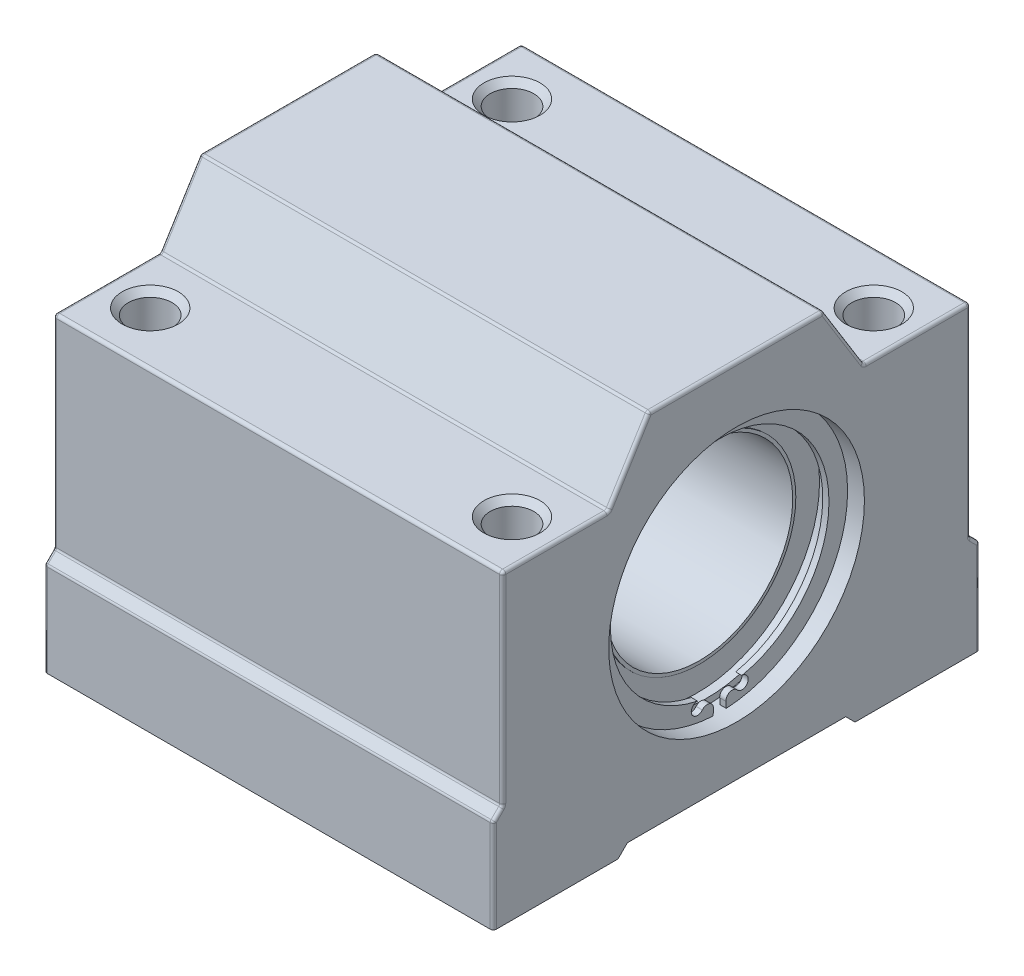
SolidWorks part; units mm, degrees
ref_plane "Front Plane" through (0, 0, 0) normal (0, 0, 1) x (1, 0, 0)
ref_plane "Top Plane" through (0, 0, 0) normal (0, 1, 0) x (1, 0, 0)
ref_plane "Right Plane" through (0, 0, 0) normal (1, 0, 0) x (0, 0, -1)
sketch "Sketch1" plane through (0, 0, 0) normal (1, 0, 0) x (0, 0, -1)
  line L1 (-19, -30) -> (-17.5, -28.5)
  line L2 (-17.5, -28.5) -> (17.5, -28.5)
  line L3 (17.5, -28.5) -> (19, -30)
  line L4 (19, -30) -> (39, -30)
  line L6 (39, -15) -> (37.5, -13.5)
  line L8 (37.5, 19) -> (20.5, 19)
  line L9 (20.5, 19) -> (14, 29.5)
  line L10 (14, 29.5) -> (-14, 29.5)
  line L11 (-14, 29.5) -> (-20.5, 19)
  line L12 (-20.5, 19) -> (-37.5, 19)
  line L15 (-39, -15) -> (-39, -30)
  line L16 (0, -28.5) -> (0, 29.5) construction
  line L17 (-16.278, 0) -> (14.0247, 0) construction
  line L18 (-39, -30) -> (-19, -30)
  line L19 (39, -15) -> (39, -30)
  line L20 (-37.5, -13.5) -> (-37.5, 19)
  line L21 (37.5, -13.5) -> (37.5, 19)
  line L22 (-29, 19) -> (-29, -30) construction
  line L23 (-29, -30) -> (29, 19) construction
  line L24 (29, 19) -> (29, -30) construction
  line L25 (-39, -15) -> (-37.5, -13.5)
  line L26 (-20.5, 0) -> (20.5, 0) construction
  circle A0 centre (0, 0) radius 20.5
  circle A1 centre (0, 0) radius 19.5
  circle A2 centre (0, 0) radius 15
  point P18 (0, 29.5)
  point P23 (0, 0)
  dimension "D12" = 30
  dimension "D1" = 78
  dimension "D2" = 49
  dimension "D3" = 30
  dimension "D5" = 59.5
  dimension "D6" = 58
  dimension "D4" = 15
  dimension "D7" = 1.5
  dimension "D8" = 28
  dimension "D9" = 1.5
  dimension "D10" = 20
  dimension "D11" = 1
extrude "Boss-Extrude1" add sketch "Sketch1" along normal blind 72 contours L25 L15 L18 L1 L2 L3 L4 L19 L6 L21 L8 L9 L10 L11 L12 L20 A0 region at (0, -29.019, 29)
extrude "Extrude-Thin1" add sketch "Sketch1<4>" along normal blind 65.5 from offset 0.5 separate body thin contours A2 thin type one direction wall 0.5
sketch "Sketch1<4>" plane through (0, 0, 0) normal (1, 0, 0) x (0, 0, -1) same geometry as "Sketch1"
extrude "Boss-Extrude2" add sketch "Sketch1<5>" along normal blind 65 from offset 0.8 contours A1 A2 region at (0, 0, 18.9485)
sketch "Sketch1<5>" plane through (0, 0, 0) normal (1, 0, 0) x (0, 0, -1) same geometry as "Sketch1"
extrude "Boss-Extrude3" add sketch "Sketch1<6>" along normal blind 67 from offset 0.3 contours A0 A1 region at (0, 0, 19.9202)
sketch "Sketch1<6>" plane through (0, 0, 0) normal (1, 0, 0) x (0, 0, -1) same geometry as "Sketch1"
ref_plane "Plane1" through (67.3, 0, 0) normal (1, 0, 0) x (0, 0, -1)
sketch "Sketch3" plane through (67.3, 0, 0) normal (1, 0, 0) x (0, 0, -1)
  line L0 (0, 0) -> (0, -50000) construction
  line L1 (-1.003, -19.4742) -> (-1.0544, -20.4729)
  line L2 (1.003, -19.4742) -> (1.0544, -20.4729)
  circle A0 centre (0, 0) radius 20.5 construction
  arc A1 (1.0544, -20.4729) -> (-1.0544, -20.4729) centre (0, 0) ccw
  circle A2 centre (0, 0) radius 19.5 construction
  arc A3 (0, -19.5) -> (1.003, -19.4742) centre (0, 0) ccw
  arc A4 (-1.003, -19.4742) -> (-2.783, -18.7751) centre (-2, -19.3972) ccw
  circle A5 centre (-2, -19.3972) radius 0.25
  arc A6 (-2.2485, -19.3699) -> (-1.7512, -19.4212) centre (0, 0) ccw
  arc A7 (-2.783, -18.7751) -> (-3.553, -17.1532) centre (-3.566, -18.1531) cw
  arc A8 (2.783, -18.7751) -> (3.553, -17.1532) centre (3.566, -18.1531) ccw
  circle A10 centre (2, -19.3972) radius 0.25
  arc A11 (1.003, -19.4742) -> (2.783, -18.7751) centre (2, -19.3972) cw
  arc A13 (3.553, -17.1532) -> (-3.553, -17.1532) centre (0, 0) ccw
  point P12 (-1.1793, -6.3921)
  dimension "D1" = 0.5
  dimension "D2" = 2
  dimension "D3" = 1
  dimension "D4" = 2
extrude "Boss-Extrude4" add sketch "Sketch3" along normal blind 1 from offset 1 contours A11 A8 A13 A7 A4 L1 A1 L2
fillet "Fillet1" radius 0.5 32 edges at (36, -13.5, -37.5) (36, -13.5, 37.5) (36, -15, 39) (36, -15, -39) (36, 19, -20.5) (36, 19, 20.5) (36, 29.5, 14) (36, 29.5, -14) (36, 19, -37.5) (36, 19, 37.5) (72, 24.25, -17.25) (72, 24.25, 17.25) (72, 2.75, 37.5) (0, -14.25, 38.25) (0, 24.25, 17.25) (72, -14.25, -38.25) (72, -22.5, -39) (72, 2.75, -37.5) (72, 29.5, 0) (72, 19, -29) (72, 19, 29) (72, -14.25, 38.25) (72, -22.5, 39) (0, -22.5, -39) (0, -14.25, -38.25) (0, 2.75, -37.5) (0, 24.25, -17.25) (0, 19, -29) (0, 29.5, 0) (0, -22.5, 39) (0, 2.75, 37.5) (0, 19, 29)
sketch "Sketch4" plane through (0, -30, 0) normal (0, -1, 0) x (1, 0, 0)
  line L0 (36, 39) -> (36, -39) construction
  line L1 (71.5, 39) -> (0.5, 39) construction
  line L2 (71.5, -39) -> (0.5, -39) construction
  line L4 (-4.9444, 29) -> (27.0918, 29) construction
  line L6 (0, 0) -> (36.1646, 0) construction
  circle A0 centre (7, 29) radius 3.5
  circle A1 centre (65, 29) radius 3.5
  circle A2 centre (65, -29) radius 3.5
  circle A3 centre (7, -29) radius 3.5
  dimension "D2" = 7
  dimension "D1" = 29
  dimension "D3" = 58
extrude "Cut-Extrude3" cut sketch "Sketch4" against normal through all
chamfer "Chamfer1" distance 1 angle 45 6 edges at (65, 19, -32.5) (7, 19, -32.5) (7, 19, 25.5) (65, 19, 25.5) (65, -30, 32.5) (7, -30, 25.5)
equation "\"D1@Boss-Extrude2\"= \"D1@Boss-Extrude1\" - 2 - 5"
equation "\"D1@Boss-Extrude3\"= \"D1@Boss-Extrude1\" - 5"
equation "\"D1@Sketch4\"= \"D6@Sketch1\" / 2"
equation "\"D1@Extrude-Thin1\"= \"D1@Boss-Extrude3\" - 1.5"
